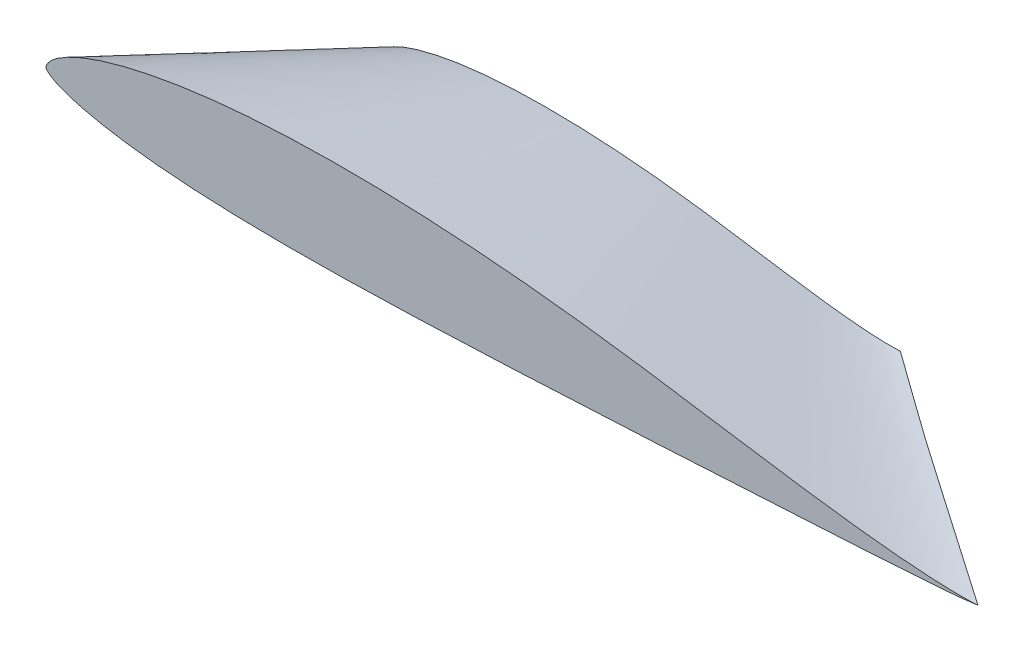
SolidWorks part; units mm, degrees
ref_plane "Front Plane" through (0, 0, 0) normal (0, 0, 1) x (1, 0, 0)
ref_plane "Top Plane" through (0, 0, 0) normal (0, 1, 0) x (1, 0, 0)
ref_plane "Right Plane" through (0, 0, 0) normal (1, 0, 0) x (0, 0, -1)
curve "Curve1"
  spline degree 3 poles (178.8235, -0.1536, 0) (180.3162, 0.0326, 0) (178.6769, -0.0979, 0) (177.3268, -0.1109, 0) (173.9976, -0.1057, 0) (169.9397, 0.1046, 0) (164.6882, 0.4858, 0) (158.5901, 1.1026, 0) (151.6988, 1.9482, 0) (144.1808, 2.9934, 0) (136.1635, 4.1927, 0) (127.7797, 5.4908, 0) (119.1442, 6.8173, 0) (110.3463, 8.0754, 0) (101.4587, 9.2, 0) (92.5465, 10.1562, 0) (83.6758, 10.9156, 0) (74.9166, 11.4682, 0) (66.342, 11.806, 0) (58.028, 11.9274, 0) (50.0487, 11.8319, 0) (42.4741, 11.515, 0) (35.367, 10.9819, 0) (28.7822, 10.24, 0) (22.7701, 9.3088, 0) (17.3773, 8.2269, 0) (12.6499, 7.0268, 0) (8.6305, 5.74, 0) (5.3502, 4.4039, 0) (2.8359, 3.0632, 0) (1.2518, 1.9009, 0) (0.4818, 1.0554, 0) (0.1891, 0.6046, 0) (0.0579, 0.3158, 0) (-0.0016, 0.0856, 0) (-0.0042, -0.0985, 0) (0.0738, -0.2696, 0) (0.2282, -0.4702, 0) (0.4808, -0.7088, 0) (0.9335, -1.0446, 0) (2.0075, -1.6855, 0) (4.0408, -2.5002, 0) (7.1529, -3.4084, 0) (11.097, -4.2605, 0) (15.8307, -5.0186, 0) (21.3187, -5.6503, 0) (27.5191, -6.1332, 0) (34.3853, -6.4628, 0) (41.8623, -6.6344, 0) (49.8874, -6.6565, 0) (58.3886, -6.5391, 0) (67.2847, -6.306, 0) (76.4836, -5.9763, 0) (85.8843, -5.5795, 0) (95.3777, -5.1338, 0) (104.8501, -4.6614, 0) (114.1865, -4.1746, 0) (123.2728, -3.6881, 0) (131.998, -3.2085, 0) (140.2557, -2.7461, 0) (147.9458, -2.3044, 0) (154.9716, -1.8945, 0) (161.2526, -1.5152, 0) (166.6878, -1.1747, 0) (171.2749, -0.8603, 0) (174.7811, -0.5984, 0) (177.6251, -0.3216, 0) (178.8235, -0.1536, 0) (180.3162, 0.0326, 0) (178.6769, -0.0979, 0) knots -0.013312 -0.00609 -0.00158 0 0.001669 0.006747 0.015187 0.026742 0.041155 0.058129 0.077283 0.098227 0.12058 0.143966 0.168018 0.192451 0.217075 0.24171 0.266182 0.29031 0.313903 0.336767 0.358704 0.37954 0.399122 0.417322 0.434037 0.449154 0.462553 0.474139 0.483848 0.491647 0.497539 0.499898 0.501005 0.501951 0.502492 0.502956 0.503431 0.504004 0.505035 0.506276 0.508636 0.515301 0.524213 0.535296 0.548467 0.563638 0.580726 0.599619 0.62018 0.642246 0.665633 0.690118 0.715452 0.741354 0.76752 0.793634 0.819375 0.844429 0.868488 0.891259 0.912467 0.93185 0.949165 0.964196 0.976755 0.986688 0.99391 0.99842 1 1.001669 1.006747 1.015187 periodic
ref_plane "Plane1" through (0, 0, -35) normal (0, 0, 1) x (1, 0, 0)
sketch "Sketch2" plane through (0, 0, 0) normal (0, 0, 1) x (1, 0, 0)
  line L0 (180, 0) -> (0, 0) construction
  spline S0 degree 3 poles (178.8235, -0.1536) (180.3162, 0.0326) (178.6769, -0.0979) (177.3268, -0.1109) (173.9976, -0.1057) (169.9397, 0.1046) (164.6882, 0.4858) (158.5901, 1.1026) (151.6988, 1.9482) (144.1808, 2.9934) (136.1635, 4.1927) (127.7797, 5.4908) (119.1442, 6.8173) (110.3463, 8.0754) (101.4587, 9.2) (92.5465, 10.1562) (83.6758, 10.9156) (74.9166, 11.4682) (66.342, 11.806) (58.028, 11.9274) (50.0487, 11.8319) (42.4741, 11.515) (35.367, 10.9819) (28.7822, 10.24) (22.7701, 9.3088) (17.3773, 8.2269) (12.6499, 7.0268) (8.6305, 5.74) (5.3502, 4.4039) (2.8359, 3.0632) (1.2518, 1.9009) (0.4818, 1.0554) (0.1891, 0.6046) (0.0579, 0.3158) (-0.0016, 0.0856) (-0.0042, -0.0985) (0.0738, -0.2696) (0.2282, -0.4702) (0.4808, -0.7088) (0.9335, -1.0446) (2.0075, -1.6855) (4.0408, -2.5002) (7.1529, -3.4084) (11.097, -4.2605) (15.8307, -5.0186) (21.3187, -5.6503) (27.5191, -6.1332) (34.3853, -6.4628) (41.8623, -6.6344) (49.8874, -6.6565) (58.3886, -6.5391) (67.2847, -6.306) (76.4836, -5.9763) (85.8843, -5.5795) (95.3777, -5.1338) (104.8501, -4.6614) (114.1865, -4.1746) (123.2728, -3.6881) (131.998, -3.2085) (140.2557, -2.7461) (147.9458, -2.3044) (154.9716, -1.8945) (161.2526, -1.5152) (166.6878, -1.1747) (171.2749, -0.8603) (174.7811, -0.5984) (177.6251, -0.3216) (178.8235, -0.1536) (180.3162, 0.0326) (178.6769, -0.0979) knots -0.013312 -0.00609 -0.00158 0 0.001669 0.006747 0.015187 0.026742 0.041155 0.058129 0.077283 0.098227 0.12058 0.143966 0.168018 0.192451 0.217075 0.24171 0.266182 0.29031 0.313903 0.336767 0.358704 0.37954 0.399122 0.417322 0.434037 0.449154 0.462553 0.474139 0.483848 0.491647 0.497539 0.499898 0.501005 0.501951 0.502492 0.502956 0.503431 0.504004 0.505035 0.506276 0.508636 0.515301 0.524213 0.535296 0.548467 0.563638 0.580726 0.599619 0.62018 0.642246 0.665633 0.690118 0.715452 0.741354 0.76752 0.793634 0.819375 0.844429 0.868488 0.891259 0.912467 0.93185 0.949165 0.964196 0.976755 0.986688 0.99391 0.99842 1 1.001669 1.006747 1.015187 only from (180, 0) to (180, 0) construction
  spline S1 degree 3 poles (178.8235, -0.1536) (180.3162, 0.0326) (178.6769, -0.0979) (177.3268, -0.1109) (173.9976, -0.1057) (169.9397, 0.1046) (164.6882, 0.4858) (158.5901, 1.1026) (151.6988, 1.9482) (144.1808, 2.9934) (136.1635, 4.1927) (127.7797, 5.4908) (119.1442, 6.8173) (110.3463, 8.0754) (101.4587, 9.2) (92.5465, 10.1562) (83.6758, 10.9156) (74.9166, 11.4682) (66.342, 11.806) (58.028, 11.9274) (50.0487, 11.8319) (42.4741, 11.515) (35.367, 10.9819) (28.7822, 10.24) (22.7701, 9.3088) (17.3773, 8.2269) (12.6499, 7.0268) (8.6305, 5.74) (5.3502, 4.4039) (2.8359, 3.0632) (1.2518, 1.9009) (0.4818, 1.0554) (0.1891, 0.6046) (0.0579, 0.3158) (-0.0016, 0.0856) (-0.0042, -0.0985) (0.0738, -0.2696) (0.2282, -0.4702) (0.4808, -0.7088) (0.9335, -1.0446) (2.0075, -1.6855) (4.0408, -2.5002) (7.1529, -3.4084) (11.097, -4.2605) (15.8307, -5.0186) (21.3187, -5.6503) (27.5191, -6.1332) (34.3853, -6.4628) (41.8623, -6.6344) (49.8874, -6.6565) (58.3886, -6.5391) (67.2847, -6.306) (76.4836, -5.9763) (85.8843, -5.5795) (95.3777, -5.1338) (104.8501, -4.6614) (114.1865, -4.1746) (123.2728, -3.6881) (131.998, -3.2085) (140.2557, -2.7461) (147.9458, -2.3044) (154.9716, -1.8945) (161.2526, -1.5152) (166.6878, -1.1747) (171.2749, -0.8603) (174.7811, -0.5984) (177.6251, -0.3216) (178.8235, -0.1536) (180.3162, 0.0326) (178.6769, -0.0979) knots -0.013312 -0.00609 -0.00158 0 0.001669 0.006747 0.015187 0.026742 0.041155 0.058129 0.077283 0.098227 0.12058 0.143966 0.168018 0.192451 0.217075 0.24171 0.266182 0.29031 0.313903 0.336767 0.358704 0.37954 0.399122 0.417322 0.434037 0.449154 0.462553 0.474139 0.483848 0.491647 0.497539 0.499898 0.501005 0.501951 0.502492 0.502956 0.503431 0.504004 0.505035 0.506276 0.508636 0.515301 0.524213 0.535296 0.548467 0.563638 0.580726 0.599619 0.62018 0.642246 0.665633 0.690118 0.715452 0.741354 0.76752 0.793634 0.819375 0.844429 0.868488 0.891259 0.912467 0.93185 0.949165 0.964196 0.976755 0.986688 0.99391 0.99842 1 1.001669 1.006747 1.015187 only from (180, 0) to (180, 0)
  point P4 (0, 0)
curve "Curve2"
  spline degree 3 poles (129.3464, -0.0853, 0) (130.1757, 0.0181, 0) (129.2649, -0.0544, 0) (128.5149, -0.0616, 0) (126.6653, -0.0587, 0) (124.4109, 0.0581, 0) (121.4935, 0.2699, 0) (118.1056, 0.6125, 0) (114.2771, 1.0823, 0) (110.1004, 1.663, 0) (105.6464, 2.3293, 0) (100.9887, 3.0504, 0) (96.1912, 3.7874, 0) (91.3035, 4.4863, 0) (86.366, 5.1111, 0) (81.4147, 5.6423, 0) (76.4865, 6.0642, 0) (71.6203, 6.3712, 0) (66.8567, 6.5589, 0) (62.2378, 6.6263, 0) (57.8048, 6.5733, 0) (53.5967, 6.3972, 0) (49.6483, 6.1011, 0) (45.9901, 5.6889, 0) (42.65, 5.1716, 0) (39.654, 4.5705, 0) (37.0277, 3.9038, 0) (34.7947, 3.1889, 0) (32.9723, 2.4466, 0) (31.5755, 1.7018, 0) (30.6954, 1.0561, 0) (30.2677, 0.5864, 0) (30.1051, 0.3359, 0) (30.0322, 0.1755, 0) (29.9991, 0.0476, 0) (29.9977, -0.0547, 0) (30.041, -0.1498, 0) (30.1268, -0.2612, 0) (30.2671, -0.3938, 0) (30.5186, -0.5803, 0) (31.1153, -0.9364, 0) (32.2449, -1.389, 0) (33.9738, -1.8935, 0) (36.165, -2.3669, 0) (38.7949, -2.7881, 0) (41.8437, -3.1391, 0) (45.2884, -3.4073, 0) (49.1029, -3.5905, 0) (53.2568, -3.6858, 0) (57.7152, -3.6981, 0) (62.4381, -3.6328, 0) (67.3804, -3.5033, 0) (72.4909, -3.3202, 0) (77.7135, -3.0997, 0) (82.9876, -2.8521, 0) (88.2501, -2.5897, 0) (93.437, -2.3192, 0) (98.4849, -2.0489, 0) (103.3322, -1.7825, 0) (107.9198, -1.5256, 0) (112.1921, -1.2802, 0) (116.0954, -1.0525, 0) (119.5848, -0.8418, 0) (122.6043, -0.6526, 0) (125.1527, -0.4779, 0) (127.1006, -0.3325, 0) (128.6806, -0.1786, 0) (129.3464, -0.0853, 0) (130.1757, 0.0181, 0) (129.2649, -0.0544, 0) knots -0.013312 -0.00609 -0.00158 0 0.001669 0.006747 0.015187 0.026742 0.041155 0.058129 0.077283 0.098227 0.12058 0.143966 0.168018 0.192451 0.217075 0.24171 0.266182 0.29031 0.313903 0.336767 0.358704 0.37954 0.399122 0.417322 0.434037 0.449154 0.462553 0.474139 0.483848 0.491647 0.497539 0.499898 0.501005 0.501951 0.502492 0.502956 0.503431 0.504004 0.505035 0.506276 0.508636 0.515301 0.524213 0.535296 0.548467 0.563638 0.580726 0.599619 0.62018 0.642246 0.665633 0.690118 0.715452 0.741354 0.76752 0.793634 0.819375 0.844429 0.868488 0.891259 0.912467 0.93185 0.949165 0.964196 0.976755 0.986688 0.99391 0.99842 1 1.001669 1.006747 1.015187 periodic
sketch "Sketch3" plane through (0, 0, -35) normal (0, 0, 1) x (1, 0, 0)
  line L0 (130, 0) -> (29.9996, 0) construction
  spline S0 degree 3 poles (129.3464, -0.0853) (130.1757, 0.0181) (129.2649, -0.0544) (128.5149, -0.0616) (126.6653, -0.0587) (124.4109, 0.0581) (121.4935, 0.2699) (118.1056, 0.6125) (114.2771, 1.0823) (110.1004, 1.663) (105.6464, 2.3293) (100.9887, 3.0504) (96.1912, 3.7874) (91.3035, 4.4863) (86.366, 5.1111) (81.4147, 5.6423) (76.4865, 6.0642) (71.6203, 6.3712) (66.8567, 6.5589) (62.2378, 6.6263) (57.8048, 6.5733) (53.5967, 6.3972) (49.6483, 6.1011) (45.9901, 5.6889) (42.65, 5.1716) (39.654, 4.5705) (37.0277, 3.9038) (34.7947, 3.1889) (32.9723, 2.4466) (31.5755, 1.7018) (30.6954, 1.0561) (30.2677, 0.5864) (30.1051, 0.3359) (30.0322, 0.1755) (29.9991, 0.0476) (29.9977, -0.0547) (30.041, -0.1498) (30.1268, -0.2612) (30.2671, -0.3938) (30.5186, -0.5803) (31.1153, -0.9364) (32.2449, -1.389) (33.9738, -1.8935) (36.165, -2.3669) (38.7949, -2.7881) (41.8437, -3.1391) (45.2884, -3.4073) (49.1029, -3.5905) (53.2568, -3.6858) (57.7152, -3.6981) (62.4381, -3.6328) (67.3804, -3.5033) (72.4909, -3.3202) (77.7135, -3.0997) (82.9876, -2.8521) (88.2501, -2.5897) (93.437, -2.3192) (98.4849, -2.0489) (103.3322, -1.7825) (107.9198, -1.5256) (112.1921, -1.2802) (116.0954, -1.0525) (119.5848, -0.8418) (122.6043, -0.6526) (125.1527, -0.4779) (127.1006, -0.3325) (128.6806, -0.1786) (129.3464, -0.0853) (130.1757, 0.0181) (129.2649, -0.0544) knots -0.013312 -0.00609 -0.00158 0 0.001669 0.006747 0.015187 0.026742 0.041155 0.058129 0.077283 0.098227 0.12058 0.143966 0.168018 0.192451 0.217075 0.24171 0.266182 0.29031 0.313903 0.336767 0.358704 0.37954 0.399122 0.417322 0.434037 0.449154 0.462553 0.474139 0.483848 0.491647 0.497539 0.499898 0.501005 0.501951 0.502492 0.502956 0.503431 0.504004 0.505035 0.506276 0.508636 0.515301 0.524213 0.535296 0.548467 0.563638 0.580726 0.599619 0.62018 0.642246 0.665633 0.690118 0.715452 0.741354 0.76752 0.793634 0.819375 0.844429 0.868488 0.891259 0.912467 0.93185 0.949165 0.964196 0.976755 0.986688 0.99391 0.99842 1 1.001669 1.006747 1.015187 only from (130, 0) to (130, 0) construction
  spline S1 degree 3 poles (129.3464, -0.0853) (130.1757, 0.0181) (129.2649, -0.0544) (128.5149, -0.0616) (126.6653, -0.0587) (124.4109, 0.0581) (121.4935, 0.2699) (118.1056, 0.6125) (114.2771, 1.0823) (110.1004, 1.663) (105.6464, 2.3293) (100.9887, 3.0504) (96.1912, 3.7874) (91.3035, 4.4863) (86.366, 5.1111) (81.4147, 5.6423) (76.4865, 6.0642) (71.6203, 6.3712) (66.8567, 6.5589) (62.2378, 6.6263) (57.8048, 6.5733) (53.5967, 6.3972) (49.6483, 6.1011) (45.9901, 5.6889) (42.65, 5.1716) (39.654, 4.5705) (37.0277, 3.9038) (34.7947, 3.1889) (32.9723, 2.4466) (31.5755, 1.7018) (30.6954, 1.0561) (30.2677, 0.5864) (30.1051, 0.3359) (30.0322, 0.1755) (29.9991, 0.0476) (29.9977, -0.0547) (30.041, -0.1498) (30.1268, -0.2612) (30.2671, -0.3938) (30.5186, -0.5803) (31.1153, -0.9364) (32.2449, -1.389) (33.9738, -1.8935) (36.165, -2.3669) (38.7949, -2.7881) (41.8437, -3.1391) (45.2884, -3.4073) (49.1029, -3.5905) (53.2568, -3.6858) (57.7152, -3.6981) (62.4381, -3.6328) (67.3804, -3.5033) (72.4909, -3.3202) (77.7135, -3.0997) (82.9876, -2.8521) (88.2501, -2.5897) (93.437, -2.3192) (98.4849, -2.0489) (103.3322, -1.7825) (107.9198, -1.5256) (112.1921, -1.2802) (116.0954, -1.0525) (119.5848, -0.8418) (122.6043, -0.6526) (125.1527, -0.4779) (127.1006, -0.3325) (128.6806, -0.1786) (129.3464, -0.0853) (130.1757, 0.0181) (129.2649, -0.0544) knots -0.013312 -0.00609 -0.00158 0 0.001669 0.006747 0.015187 0.026742 0.041155 0.058129 0.077283 0.098227 0.12058 0.143966 0.168018 0.192451 0.217075 0.24171 0.266182 0.29031 0.313903 0.336767 0.358704 0.37954 0.399122 0.417322 0.434037 0.449154 0.462553 0.474139 0.483848 0.491647 0.497539 0.499898 0.501005 0.501951 0.502492 0.502956 0.503431 0.504004 0.505035 0.506276 0.508636 0.515301 0.524213 0.535296 0.548467 0.563638 0.580726 0.599619 0.62018 0.642246 0.665633 0.690118 0.715452 0.741354 0.76752 0.793634 0.819375 0.844429 0.868488 0.891259 0.912467 0.93185 0.949165 0.964196 0.976755 0.986688 0.99391 0.99842 1 1.001669 1.006747 1.015187 only from (130, 0) to (130, 0)
loft "Loft1" add profiles "Sketch2", "Sketch3" connector at (55.3868, 11.8834, 0) connector at (61.3985, 6.6053, -35)
mirror "Mirror1" [suppressed] about plane through (0, 0, 0) normal (0, 0, 1)
ref_axis "Axis4" through (0, 0, -61.6271) along (0, 0, 1)
ref_axis "Axis1" through (180, 0, 0) along (-1, 0, 0)
ref_axis "Axis2" through (130, 0, -35) along (-1, 0, 0)
ref_point "Point1"
ref_axis "Axis3" through (-0.0007, 0, 0) along (0.6508, 0, -0.7593)
sketch "Sketch4" plane through (0, 0, 0) normal (0, 1, 0) x (1, 0, 0)
  line L0 (0, 0) -> (141.8779, 107.8393) construction
  line L1 (0, 0) -> (100, 360) construction
  line L3 (25.3509, 91.2632) -> (60.0348, 45.6316) construction
  line L4 (94.7187, 0) -> (60.0348, 45.6316) construction
  line L5 (180, 0) -> (0, 0) construction
  dimension "D1" = 360
  dimension "D2" = 100
ref_plane "Plane2" through (0, 0, 0) normal (0.6051, 0, 0.7961) x (0.7961, 0, -0.6051)
sketch "Sketch5" plane through (0, 0, 0) normal (0.6051, 0, 0.7961) x (0.7961, 0, -0.6051)
  line L0 (42.0724, -26.6467) -> (64.7445, 35.6444) construction
  line L1 (42.0724, -26.6467) -> (42.0724, 24.9899) construction
  dimension "D1" = 20
ref_axis "Axis5" through (33.7471, -25.7769, -25.6507) along (0.2723, 0.9397, -0.207)
ref_point "Point2"
